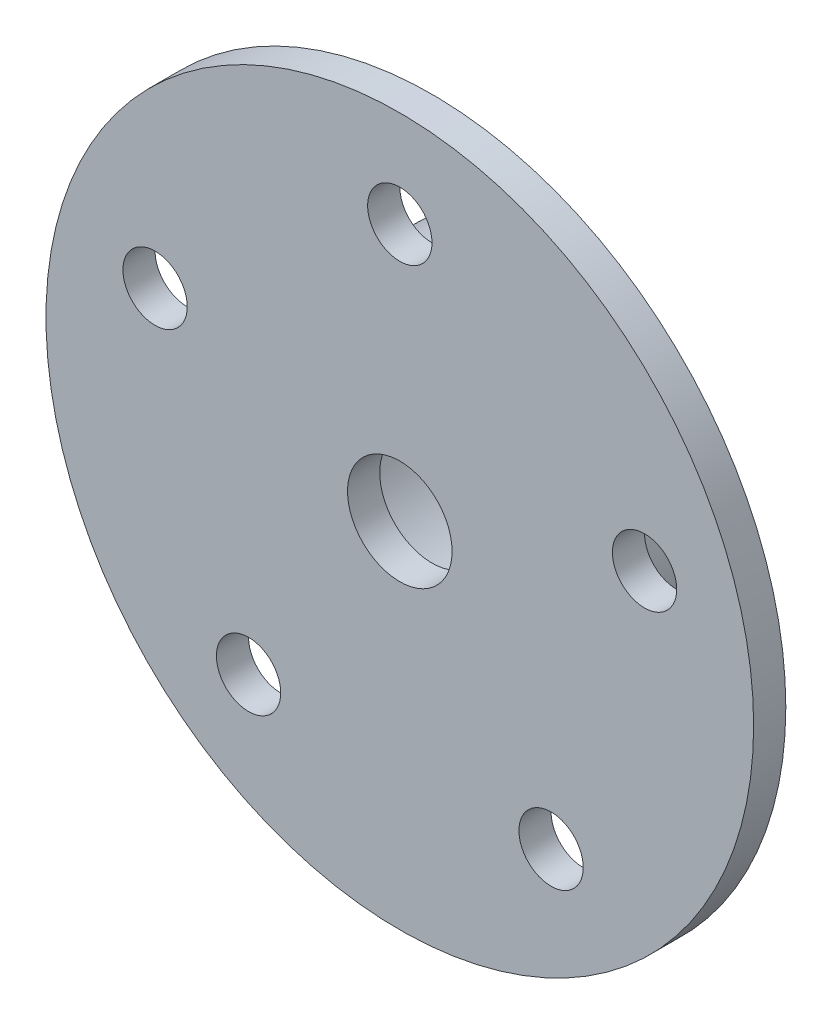
SolidWorks part; units mm, degrees
ref_plane "前视基准面" through (0, 0, 0) normal (0, 0, 1) x (1, 0, 0)
ref_plane "上视基准面" through (0, 0, 0) normal (0, 1, 0) x (1, 0, 0)
ref_plane "右视基准面" through (0, 0, 0) normal (1, 0, 0) x (0, 0, -1)
other "Configuration Table"
sketch "草图1" plane through (0, 0, 0) normal (0, 0, 1) x (1, 0, 0)
  circle A4 centre (0, 0) radius 3.25
  circle A5 centre (0, 0) radius 22
  circle A6 centre (0, 0) radius 16 construction
  circle A8 centre (0, 16) radius 2
  circle A9 centre (15.2169, 4.9443) radius 2
  circle A10 centre (9.4046, -12.9443) radius 2
  circle A11 centre (-9.4046, -12.9443) radius 2
  circle A12 centre (-15.2169, 4.9443) radius 2
  point P0 (0, 0)
  point P17 (0, 0)
  point P19 (0, 0)
  dimension "D3" = 5
  dimension "D5" = 4
  dimension "D1" = 44
  dimension "D2" = 32
  dimension "D4" = 6.5
extrude "凸台-拉伸1" add sketch "草图1" along normal blind 2
sketch "草图3" plane through (0, 0, 0) normal (0, 0, -1) x (-1, 0, 0)
  circle A0 centre (0, 0) radius 11
  circle A1 centre (0, 0) radius 7.6
  dimension "D1" = 22
  dimension "D2" = 15.2
extrude "凸台-拉伸2" add sketch "草图3" along normal blind 7
